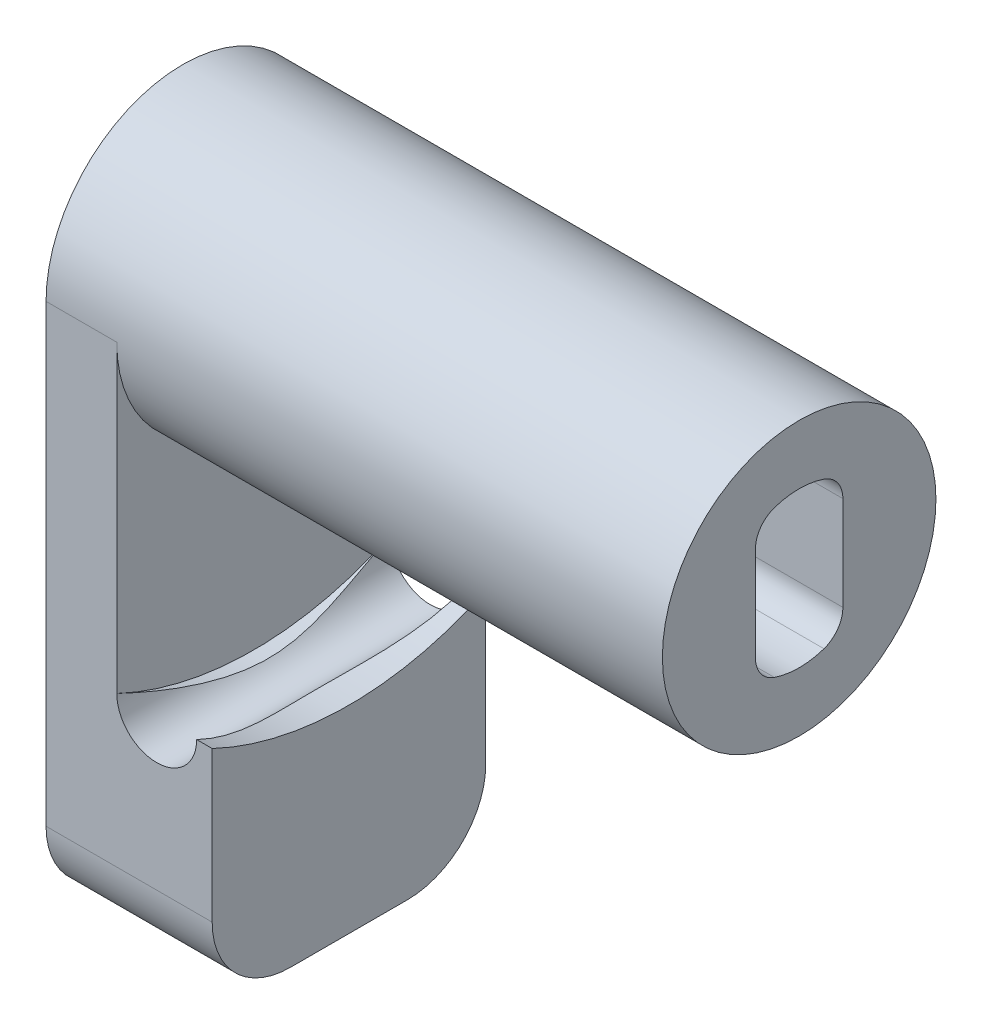
SolidWorks part; units mm, degrees
material "ABS"
ref_plane "Front Plane" through (0, 0, 0) normal (1, 0, 0) x (0, 1, 0)
ref_plane "Top Plane" through (0, 0, 0) normal (0, 0, 1) x (0, 1, 0)
ref_plane "Right Plane" through (0, 0, 0) normal (0, 1, 0) x (-1, 0, 0)
sketch "Sketch1" plane through (0, 0, 0) normal (1, 0, 0) x (0, 1, 0)
  circle A2 centre (0, 0) radius 8.7376
  dimension "D3" = 17.4752
extrude "Boss-Extrude1" add sketch "Sketch1" along normal blind 39.37 contours A2 region at (0, 0, 0)
sketch "Sketch10" plane through (0, 0, 0) normal (-1, 0, 0) x (0, -1, 0)
  line L0 (0, 8.7376) -> (34.036, 8.7376)
  line L2 (34.036, 8.7376) -> (34.036, -8.7376)
  line L3 (34.036, -8.7376) -> (0, -8.7376)
  circle A0 centre (0, 0) radius 8.7376 construction
  arc A2 (0, 8.7376) -> (0, -8.7376) centre (0, 0) cw
  dimension "D1" = 34.036
extrude "Boss-Extrude3" add sketch "Sketch10" against normal blind 4.516 contours L0 A2 L3 L2 region at (0, -20.3793, 0)
fillet "Fillet2" radius 5 2 edges at (2.258, -34.036, 8.7376) (2.258, -34.036, -8.7376)
sketch "Sketch14" [suppressed] plane through (0, 0, 0) normal (-1, 0, 0) x (0, 0, 1)
  line L0 (0.5115, -3.4237) -> (0.3944, -4.0089)
  line L1 (0, 0) -> (0, -4.064) construction
  line L2 (0, 0) -> (0.5606, -3.4335) construction
  line L3 (0.6039, -3.4087) -> (0.9011, -3.9262)
  line L4 (-0.6903, -3.3922) -> (-1.0005, -3.9021)
  line L5 (-0.5983, -3.4096) -> (-0.4961, -3.9976)
  line L6 (-1.8089, -2.9515) -> (-2.2748, -3.3245)
  line L7 (-1.7284, -2.9994) -> (-1.8334, -3.5869)
  line L8 (-2.7093, -2.1549) -> (-3.2746, -2.346)
  line L9 (-2.65, -2.2273) -> (-2.9496, -2.7435)
  line L10 (-3.2829, -1.0983) -> (-3.8795, -1.0846)
  line L11 (-3.252, -1.1867) -> (-3.7101, -1.5692)
  line L12 (-3.4605, 0.0907) -> (-4.0165, 0.3077)
  line L13 (-3.4617, -0.0029) -> (-4.023, -0.2057)
  line L14 (-3.2208, 1.2689) -> (-3.669, 1.6629)
  line L15 (-3.2539, 1.1813) -> (-3.8507, 1.1827)
  line L16 (-2.5926, 2.2939) -> (-2.879, 2.8175)
  line L17 (-2.6537, 2.223) -> (-3.214, 2.4284)
  line L18 (-1.6517, 3.0423) -> (-1.7417, 3.6323)
  line L19 (-1.7333, 2.9965) -> (-2.1896, 3.3812)
  line L20 (-0.5115, 3.4237) -> (-0.3944, 4.0089)
  line L21 (-0.6039, 3.4087) -> (-0.9011, 3.9262)
  line L22 (0.6903, 3.3922) -> (1.0005, 3.9021)
  line L23 (0.5983, 3.4096) -> (0.4961, 3.9976)
  line L24 (1.8089, 2.9515) -> (2.2748, 3.3245)
  line L25 (1.7284, 2.9994) -> (1.8334, 3.5869)
  line L26 (2.7093, 2.1549) -> (3.2746, 2.346)
  line L27 (2.65, 2.2273) -> (2.9496, 2.7435)
  line L28 (3.2829, 1.0983) -> (3.8795, 1.0846)
  line L29 (3.252, 1.1867) -> (3.7101, 1.5692)
  line L30 (3.4605, -0.0907) -> (4.0165, -0.3077)
  line L31 (3.4617, 0.0029) -> (4.023, 0.2057)
  line L32 (3.2208, -1.2689) -> (3.669, -1.6629)
  line L33 (3.2539, -1.1813) -> (3.8507, -1.1827)
  line L34 (2.5926, -2.2939) -> (2.879, -2.8175)
  line L35 (2.6537, -2.223) -> (3.214, -2.4284)
  line L36 (1.6517, -3.0423) -> (1.7417, -3.6323)
  line L37 (1.7333, -2.9965) -> (2.1896, -3.3812)
  line L38 (-0.1032, -4.0627) -> (0, -4.064)
  line L39 (-1.4865, -3.7824) -> (-1.39, -3.8189)
  line L40 (-2.6905, -3.0459) -> (-2.6123, -3.1132)
  line L41 (-3.5195, -2.032) -> (-3.57, -1.942)
  line L42 (-4.0023, -0.7057) -> (-4.0189, -0.6039)
  line L43 (-4.0023, 0.7057) -> (-3.9831, 0.8071)
  line L44 (-3.5195, 2.032) -> (-3.4668, 2.1207)
  line L45 (-2.6123, 3.1132) -> (-2.5324, 3.1785)
  line L46 (-1.39, 3.8189) -> (-1.2926, 3.853)
  line L47 (0, 4.064) -> (0.1032, 4.0627)
  line L48 (1.39, 3.8189) -> (1.4865, 3.7824)
  line L49 (2.6123, 3.1132) -> (2.6905, 3.0459)
  line L50 (3.5195, 2.032) -> (3.57, 1.942)
  line L51 (4.0023, 0.7057) -> (4.0189, 0.6039)
  line L52 (4.0023, -0.7057) -> (3.9831, -0.8071)
  line L53 (3.5195, -2.032) -> (3.4668, -2.1207)
  line L54 (2.6123, -3.1132) -> (2.5324, -3.1785)
  line L55 (1.39, -3.8189) -> (1.2926, -3.853)
  arc A0 (0.3497, -4.0489) -> (0, -4.064) centre (0, 0) cw
  arc A1 (0.3497, -4.0489) -> (0.3944, -4.0089) centre (0.3454, -3.9991) ccw
  arc A2 (0.5115, -3.4237) -> (0.6039, -3.4087) centre (0.5606, -3.4335) cw
  arc A3 (0.4203, -4.0631) -> (0.3944, -4.0089) centre (0.4434, -4.0187) cw
  arc A4 (0.4203, -4.0631) -> (0.7372, -4.2116) centre (2.3016, -0.4608) ccw
  arc A6 (0.9562, -3.9499) -> (0.9011, -3.9262) centre (0.9445, -3.9013) cw
  arc A7 (0.9562, -3.9499) -> (1.2926, -3.853) centre (0, 0) ccw
  arc A8 (-1.0562, -3.9243) -> (-1.39, -3.8189) centre (0, 0) cw
  arc A9 (-1.0562, -3.9243) -> (-1.0005, -3.9021) centre (-1.0432, -3.8761) ccw
  arc A10 (-0.6903, -3.3922) -> (-0.5983, -3.4096) centre (-0.6476, -3.4182) cw
  arc A11 (-0.4524, -4.0387) -> (-0.4961, -3.9976) centre (-0.4468, -3.9891) cw
  arc A12 (-0.4524, -4.0387) -> (-0.1032, -4.0627) centre (0, 0) ccw
  arc A13 (-2.3347, -3.3264) -> (-2.6123, -3.1132) centre (0, 0) cw
  arc A14 (-2.3347, -3.3264) -> (-2.2748, -3.3245) centre (-2.306, -3.2855) ccw
  arc A15 (-1.8089, -2.9515) -> (-1.7284, -2.9994) centre (-1.7776, -2.9906) cw
  arc A16 (-1.8064, -3.6405) -> (-1.8334, -3.5869) centre (-1.7842, -3.5957) cw
  arc A17 (-1.8064, -3.6405) -> (-1.4865, -3.7824) centre (0, 0) ccw
  arc A18 (-3.3316, -2.3273) -> (-3.5195, -2.032) centre (0, 0) cw
  arc A19 (-3.3316, -2.3273) -> (-3.2746, -2.346) centre (-3.2906, -2.2987) ccw
  arc A20 (-2.7093, -2.1549) -> (-2.65, -2.2273) centre (-2.6933, -2.2022) cw
  arc A21 (-2.9426, -2.8031) -> (-2.9496, -2.7435) centre (-2.9064, -2.7686) cw
  arc A22 (-2.9426, -2.8031) -> (-2.6905, -3.0459) centre (0, 0) ccw
  arc A23 (-3.9267, -1.0475) -> (-4.0023, -0.7057) centre (0, 0) cw
  arc A24 (-3.9267, -1.0475) -> (-3.8795, -1.0846) centre (-3.8784, -1.0346) ccw
  arc A25 (-3.2829, -1.0983) -> (-3.252, -1.1867) centre (-3.284, -1.1483) cw
  arc A26 (-3.7238, -1.6276) -> (-3.7101, -1.5692) centre (-3.678, -1.6076) cw
  arc A27 (-3.7238, -1.6276) -> (-3.57, -1.942) centre (0, 0) ccw
  arc A28 (-4.0481, 0.3587) -> (-4.0023, 0.7057) centre (0, 0) cw
  arc A29 (-4.0481, 0.3587) -> (-4.0165, 0.3077) centre (-3.9983, 0.3543) ccw
  arc A30 (-3.4605, 0.0907) -> (-3.4617, -0.0029) centre (-3.4787, 0.0442) cw
  arc A31 (-4.0559, -0.2558) -> (-4.023, -0.2057) centre (-4.006, -0.2527) cw
  arc A32 (-4.0559, -0.2558) -> (-4.0189, -0.6039) centre (0, 0) ccw
  arc A33 (-3.6813, 1.7216) -> (-3.5195, 2.032) centre (0, 0) cw
  arc A34 (-3.6813, 1.7216) -> (-3.669, 1.6629) centre (-3.636, 1.7005) ccw
  arc A35 (-3.2208, 1.2689) -> (-3.2539, 1.1813) centre (-3.2538, 1.2313) cw
  arc A36 (-3.8988, 1.1468) -> (-3.8507, 1.1827) centre (-3.8509, 1.1327) cw
  arc A37 (-3.8988, 1.1468) -> (-3.9831, 0.8071) centre (0, 0) ccw
  arc A38 (-2.8705, 2.8769) -> (-2.6123, 3.1132) centre (0, 0) cw
  arc A39 (-2.8705, 2.8769) -> (-2.879, 2.8175) centre (-2.8352, 2.8415) ccw
  arc A40 (-2.5926, 2.2939) -> (-2.6537, 2.223) centre (-2.6365, 2.2699) cw
  arc A41 (-3.2715, 2.4111) -> (-3.214, 2.4284) centre (-3.2312, 2.3815) cw
  arc A42 (-3.2715, 2.4111) -> (-3.4668, 2.1207) centre (0, 0) ccw
  arc A43 (-1.7134, 3.6852) -> (-1.39, 3.8189) centre (0, 0) cw
  arc A44 (-1.7134, 3.6852) -> (-1.7417, 3.6323) centre (-1.6923, 3.6398) ccw
  arc A45 (-1.6517, 3.0423) -> (-1.7333, 2.9965) centre (-1.7011, 3.0348) cw
  arc A46 (-2.2495, 3.3846) -> (-2.1896, 3.3812) centre (-2.2218, 3.343) cw
  arc A47 (-2.2495, 3.3846) -> (-2.5324, 3.1785) centre (0, 0) ccw
  arc A48 (-0.3497, 4.0489) -> (0, 4.064) centre (0, 0) cw
  arc A49 (-0.3497, 4.0489) -> (-0.3944, 4.0089) centre (-0.3454, 3.9991) ccw
  arc A50 (-0.5115, 3.4237) -> (-0.6039, 3.4087) centre (-0.5606, 3.4335) cw
  arc A51 (-0.9562, 3.9499) -> (-0.9011, 3.9262) centre (-0.9445, 3.9013) cw
  arc A52 (-0.9562, 3.9499) -> (-1.2926, 3.853) centre (0, 0) ccw
  arc A53 (1.0562, 3.9243) -> (1.39, 3.8189) centre (0, 0) cw
  arc A54 (1.0562, 3.9243) -> (1.0005, 3.9021) centre (1.0432, 3.8761) ccw
  arc A55 (0.6903, 3.3922) -> (0.5983, 3.4096) centre (0.6476, 3.4182) cw
  arc A56 (0.4524, 4.0387) -> (0.4961, 3.9976) centre (0.4468, 3.9891) cw
  arc A57 (0.4524, 4.0387) -> (0.1032, 4.0627) centre (0, 0) ccw
  arc A58 (2.3347, 3.3264) -> (2.6123, 3.1132) centre (0, 0) cw
  arc A59 (2.3347, 3.3264) -> (2.2748, 3.3245) centre (2.306, 3.2855) ccw
  arc A60 (1.8089, 2.9515) -> (1.7284, 2.9994) centre (1.7776, 2.9906) cw
  arc A61 (1.8064, 3.6405) -> (1.8334, 3.5869) centre (1.7842, 3.5957) cw
  arc A62 (1.8064, 3.6405) -> (1.4865, 3.7824) centre (0, 0) ccw
  arc A63 (3.3316, 2.3273) -> (3.5195, 2.032) centre (0, 0) cw
  arc A64 (3.3316, 2.3273) -> (3.2746, 2.346) centre (3.2906, 2.2987) ccw
  arc A65 (2.7093, 2.1549) -> (2.65, 2.2273) centre (2.6933, 2.2022) cw
  arc A66 (2.9426, 2.8031) -> (2.9496, 2.7435) centre (2.9064, 2.7686) cw
  arc A67 (2.9426, 2.8031) -> (2.6905, 3.0459) centre (0, 0) ccw
  arc A68 (3.9267, 1.0475) -> (4.0023, 0.7057) centre (0, 0) cw
  arc A69 (3.9267, 1.0475) -> (3.8795, 1.0846) centre (3.8784, 1.0346) ccw
  arc A70 (3.2829, 1.0983) -> (3.252, 1.1867) centre (3.284, 1.1483) cw
  arc A71 (3.7238, 1.6276) -> (3.7101, 1.5692) centre (3.678, 1.6076) cw
  arc A72 (3.7238, 1.6276) -> (3.57, 1.942) centre (0, 0) ccw
  arc A73 (4.0481, -0.3587) -> (4.0023, -0.7057) centre (0, 0) cw
  arc A74 (4.0481, -0.3587) -> (4.0165, -0.3077) centre (3.9983, -0.3543) ccw
  arc A75 (3.4605, -0.0907) -> (3.4617, 0.0029) centre (3.4787, -0.0442) cw
  arc A76 (4.0559, 0.2558) -> (4.023, 0.2057) centre (4.006, 0.2527) cw
  arc A77 (4.0559, 0.2558) -> (4.0189, 0.6039) centre (0, 0) ccw
  arc A78 (3.6813, -1.7216) -> (3.5195, -2.032) centre (0, 0) cw
  arc A79 (3.6813, -1.7216) -> (3.669, -1.6629) centre (3.636, -1.7005) ccw
  arc A80 (3.2208, -1.2689) -> (3.2539, -1.1813) centre (3.2538, -1.2313) cw
  arc A81 (3.8988, -1.1468) -> (3.8507, -1.1827) centre (3.8509, -1.1327) cw
  arc A82 (3.8988, -1.1468) -> (3.9831, -0.8071) centre (0, 0) ccw
  arc A83 (2.8705, -2.8769) -> (2.6123, -3.1132) centre (0, 0) cw
  arc A84 (2.8705, -2.8769) -> (2.879, -2.8175) centre (2.8352, -2.8415) ccw
  arc A85 (2.5926, -2.2939) -> (2.6537, -2.223) centre (2.6365, -2.2699) cw
  arc A86 (3.2715, -2.4111) -> (3.214, -2.4284) centre (3.2312, -2.3815) cw
  arc A87 (3.2715, -2.4111) -> (3.4668, -2.1207) centre (0, 0) ccw
  arc A88 (1.7134, -3.6852) -> (1.39, -3.8189) centre (0, 0) cw
  arc A89 (1.7134, -3.6852) -> (1.7417, -3.6323) centre (1.6923, -3.6398) ccw
  arc A90 (1.6517, -3.0423) -> (1.7333, -2.9965) centre (1.7011, -3.0348) cw
  arc A91 (2.2495, -3.3846) -> (2.1896, -3.3812) centre (2.2218, -3.343) cw
  arc A92 (2.2495, -3.3846) -> (2.5324, -3.1785) centre (0, 0) ccw
  point P207 (0, 0)
  dimension "D1" = 4.064
  dimension "D2" = 0.05
  dimension "D3" = 0.05
  dimension "D4" = 0.04
  dimension "D5" = 18
  dimension "D6" = 0.5968
  dimension "D8" = 0.35
sketch "Sketch15" plane through (4.516, 0, 0) normal (1, 0, 0) x (0, 1, 0)
  line L1 (-29.036, 8.7376) -> (-18.796, 8.7376)
  line L2 (-18.796, 8.7376) -> (-18.796, -8.7376)
  line L3 (0, 8.7376) -> (-29.036, 8.7376) construction
  line L4 (-29.036, -8.7376) -> (-18.796, -8.7376)
  line L5 (-34.036, 3.7376) -> (-34.036, -3.7376) construction
  line L6 (-34.036, 3.7376) -> (-34.036, -3.7376)
  line L8 (-29.036, -8.7376) -> (0, -8.7376) construction
  line L13 (0, 8.7376) -> (-29.036, 8.7376)
  line L14 (-34.036, 3.7376) -> (-34.036, -3.7376)
  line L15 (-29.036, -8.7376) -> (0, -8.7376)
  line L17 (-34.036, 3.7376) -> (-34.036, -3.7376)
  arc A0 (-29.036, 8.7376) -> (-34.036, 3.7376) centre (-29.036, 3.7376) ccw construction
  arc A1 (-34.036, -3.7376) -> (-29.036, -8.7376) centre (-29.036, -3.7376) ccw construction
  arc A2 (-29.036, 8.7376) -> (-34.036, 3.7376) centre (-29.036, 3.7376) ccw
  arc A3 (-34.036, -3.7376) -> (-29.036, -8.7376) centre (-29.036, -3.7376) ccw
  arc A7 (-29.036, 8.7376) -> (-34.036, 3.7376) centre (-29.036, 3.7376) ccw
  arc A8 (-34.036, -3.7376) -> (-29.036, -8.7376) centre (-29.036, -3.7376) ccw
  arc A9 (0, 8.7376) -> (0, -8.7376) centre (0, 0) ccw
  arc A10 (-29.036, 8.7376) -> (-34.036, 3.7376) centre (-29.036, 3.7376) ccw
  arc A11 (-34.036, -3.7376) -> (-29.036, -8.7376) centre (-29.036, -3.7376) ccw
  arc A12 (0, 8.7376) -> (0, -8.7376) centre (0, 0) ccw
  line M2 (0, 8.7376) -> (-29.036, 8.7376)
  arc M3 (-29.036, 8.7376) -> (-34.036, 3.7376) centre (-29.036, 3.7376) ccw
  line M4 (-34.036, 3.7376) -> (-34.036, -3.7376)
  arc M5 (-34.036, -3.7376) -> (-29.036, -8.7376) centre (-29.036, -3.7376) ccw
  dimension "D1" = 15.24
  dimension "D2" = 0
extrude "Boss-Extrude4" add sketch "Sketch15" along normal blind 6.096 contours M2 M3 M4 M5 region at (4.516, -26.143, 0)
sketch "Sketch21" plane through (10.612, 0, 0) normal (1, 0, 0) x (0, 1, 0)
  line L2 (-18.796, -8.7376) -> (-18.796, 8.7376)
  line L4 (-29.036, 8.7376) -> (-18.796, 8.7376) construction
  line L5 (-19.431, -8.7376) -> (-18.796, -8.7376)
  line L6 (-18.796, 8.7376) -> (-18.796, -8.7376) construction
  line L8 (-18.796, -8.7376) -> (0, -8.7376) construction
  line L14 (-18.796, -8.7376) -> (-18.796, 8.7376) construction
  line L20 (-18.796, 8.7376) -> (-29.036, 8.7376)
  arc A2 (-19.431, -8.7376) -> (-19.431, 8.7376) centre (-1.0855, 0) cw
  dimension "D4" = 20.32
  dimension "D2" = 0.635
  dimension "D3" = 0.635
extrude "Cut-Extrude8" cut sketch "Sketch21" against normal up to surface (6.096 mm away) contours A2 L2 region at (10.612, -19.8652, 0) up to face at (4.516, -11.5824, 0)
sketch "Sketch22" plane through (39.37, 0, 0) normal (1, 0, 0) x (0, 1, 0)
  line L7 (-4.0897, -2.794) -> (4.0897, 2.794) construction
  line L8 (-4.0897, 2.794) -> (4.0897, -2.794) construction
  line L11 (-4.0897, -2.794) -> (4.0897, -2.794)
  line L13 (-4.0897, 2.794) -> (4.0897, 2.794)
  line L15 (-4.0897, -2.794) -> (4.0897, 2.794) construction
  line L16 (-4.0897, 2.794) -> (4.0897, -2.794) construction
  arc A3 (-4.0897, 2.794) -> (-4.0897, -2.794) centre (0, 0) ccw
  arc A4 (4.0897, -2.794) -> (4.0897, 2.794) centre (0, 0) ccw
  dimension "D2" = 9.906
  dimension "D3" = 5.588
extrude "Cut-Extrude10" cut sketch "Sketch22" against normal blind 12.192
fillet "Fillet11" radius 1.778 4 edges at (33.274, 4.0897, -2.794) (33.274, 4.0897, 2.794) (33.274, -4.0897, -2.794) (33.274, -4.0897, 2.794)
sketch "Sketch25" plane through (0, 0, -8.7376) normal (0, 0, -1) x (1, 0, 0)
  line L3 (4.516, 19.431) -> (4.516, 0) construction
  line L4 (4.516, 19.431) -> (10.612, 19.431) construction
  circle A0 centre (7.0687, 19.431) radius 2.5527
  dimension "D1" = 5.1054
extrude "Cut-Extrude14" cut sketch "Sketch25" against normal through all
sketch "Sketch26" plane through (0, 0, 0) normal (-1, 0, 0) x (0, -1, 0)
  line L1 (3.7411, 1.5875) -> (5.3921, 1.5875)
  line L2 (3.7411, 1.5875) -> (3.7411, -1.5875) construction
  line L3 (3.7411, -1.5875) -> (5.3921, -1.5875)
  line L4 (5.3921, 1.5875) -> (5.3921, -1.5875)
  arc A0 (3.7411, 1.5875) -> (3.7411, -1.5875) centre (0, 0) ccw
  dimension "D1" = 8.128
  dimension "D2" = 3.175
  dimension "D3" = 1.651
extrude "Cut-Extrude15" cut sketch "Sketch26" against normal blind 21.59
fillet "Fillet12" radius 0.3969 4 edges at (10.795, -3.7411, 1.5875) (10.795, -5.3921, 1.5875) (10.795, -3.7411, -1.5875) (10.795, -5.3921, -1.5875)
